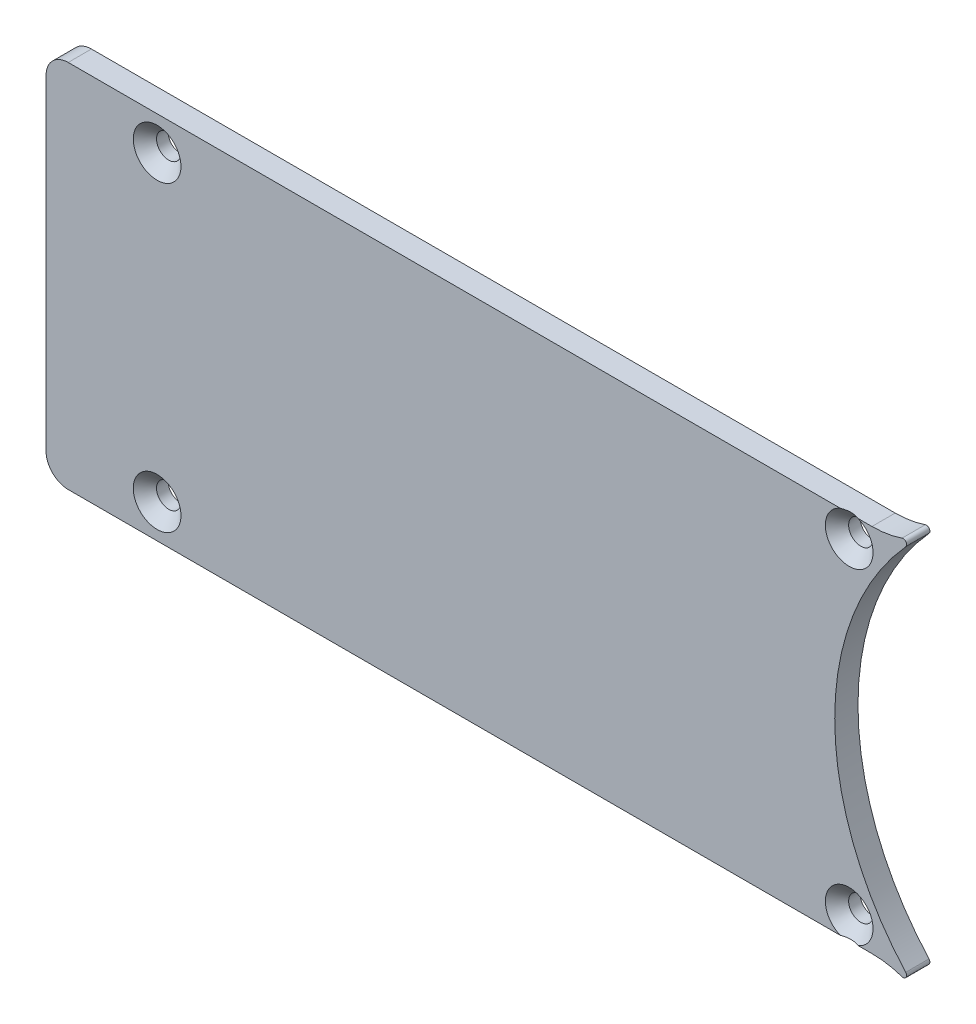
SolidWorks part; units mm, degrees
ref_plane "前视基准面" through (0, 0, 0) normal (0, 0, 1) x (1, 0, 0)
ref_plane "上视基准面" through (0, 0, 0) normal (0, 1, 0) x (1, 0, 0)
ref_plane "右视基准面" through (0, 0, 0) normal (1, 0, 0) x (0, 0, -1)
sketch "草图1" plane through (0, 0, -0.4966) normal (0, 0, 1) x (1, 0, 0)
  line L2 (-91.4, -10.1) -> (-91.4, -14)
  line L3 (-89.5, -15.9) -> (-20.4022, -15.9)
  line L4 (-20.4022, 15.9) -> (-89.5, 15.9)
  line L5 (-91.4, 14) -> (-91.4, 10.1)
  line L8 (-91.4, 10.1) -> (-91.4, -10.1)
  arc A3 (-91.4, -14) -> (-89.5, -15.9) centre (-89.5, -14) ccw
  arc A5 (-17.8134, -16.3248) -> (-20.4022, -15.9) centre (-20.4022, -24) ccw
  arc A16 (-23.6, 0) -> (-17.4951, -15.8392) centre (0, 0) ccw
  arc A17 (-17.4951, 15.8392) -> (-23.6, 0) centre (0, 0) ccw
  arc A18 (-20.4022, 15.9) -> (-17.8134, 16.3248) centre (-20.4022, 24) ccw
  arc A19 (-89.5, 15.9) -> (-91.4, 14) centre (-89.5, 14) ccw
  arc A20 (-17.4951, 15.8392) -> (-17.8134, 16.3248) centre (-17.7175, 16.0406) ccw
  arc A21 (-17.8134, -16.3248) -> (-17.4951, -15.8392) centre (-17.7175, -16.0406) ccw
  circle A24 centre (-81.856, 13) radius 1.05
  circle A25 centre (-81.856, 13) radius 1.05
  circle A39 centre (-81.856, -13) radius 1.05
  circle A40 centre (-81.856, -13) radius 1.05
  circle A42 centre (-22.356, -14) radius 1.05
  circle A43 centre (-22.356, -14) radius 1.05
  circle A45 centre (-22.356, 14) radius 1.05
  circle A46 centre (-22.356, 14) radius 1.05
  dimension "D1" = 0.3
  dimension "D2" = 0.1
  dimension "D3" = 0.1
  dimension "D4" = 0.1
  dimension "D5" = 0.1
extrude "凸台-拉伸1" add sketch "草图1" along normal blind 2
sketch "草图2" plane through (0, 0, -0.4966) normal (0, 0, 1) x (1, 0, 0)
  line L0 (-91.4, 0) -> (-22.0793, 0.4611) construction
  line L1 (-66.7396, 11.2306) -> (-46.7396, 11.2306)
  line L2 (-67.7396, 10.2306) -> (-67.7396, -9.7694)
  line L3 (-66.7396, -10.7694) -> (-46.7396, -10.7694)
  line L4 (-45.7396, 10.2306) -> (-45.7396, -9.7694)
  line L5 (-67.7396, 11.2306) -> (-45.7396, -10.7694) construction
  line L6 (-67.7396, -10.7694) -> (-45.7396, 11.2306) construction
  line L7 (-91.4, 14) -> (-91.4, -14) construction
  line L8 (-68.2396, 12.7306) -> (-45.2396, 12.7306)
  line L9 (-44.2396, 11.7306) -> (-44.2396, -11.2694)
  line L10 (-68.2396, -12.2694) -> (-45.2396, -12.2694)
  line L11 (-69.2396, 11.7306) -> (-69.2396, -11.2694)
  line L12 (-67.7396, 11.2306) -> (-67.7396, -10.7694) construction
  line L13 (-67.7396, -10.7694) -> (-45.7396, -10.7694) construction
  line L14 (-45.7396, 11.2306) -> (-45.7396, -10.7694) construction
  line L15 (-67.7396, 11.2306) -> (-45.7396, 11.2306) construction
  line L16 (-69.2396, 12.7306) -> (-44.2396, 12.7306) construction
  line L17 (-44.2396, 12.7306) -> (-44.2396, -12.2694) construction
  line L18 (-69.2396, -12.2694) -> (-44.2396, -12.2694) construction
  line L19 (-69.2396, 12.7306) -> (-69.2396, -12.2694) construction
  arc A0 (-67.7396, -9.7694) -> (-66.7396, -10.7694) centre (-66.7396, -9.7694) ccw
  arc A1 (-46.7396, -10.7694) -> (-45.7396, -9.7694) centre (-46.7396, -9.7694) ccw
  arc A2 (-46.7396, 11.2306) -> (-45.7396, 10.2306) centre (-46.7396, 10.2306) cw
  arc A3 (-66.7396, 11.2306) -> (-67.7396, 10.2306) centre (-66.7396, 10.2306) ccw
  arc A4 (-45.2396, 12.7306) -> (-44.2396, 11.7306) centre (-45.2396, 11.7306) cw
  arc A5 (-44.2396, -11.2694) -> (-45.2396, -12.2694) centre (-45.2396, -11.2694) cw
  arc A6 (-68.2396, -12.2694) -> (-69.2396, -11.2694) centre (-68.2396, -11.2694) cw
  arc A7 (-68.2396, 12.7306) -> (-69.2396, 11.7306) centre (-68.2396, 11.7306) ccw
  point P0 (-56.7396, 0.2306)
  point P11 (-56.7396, 0.2306)
  dimension "D4" = 1
  dimension "D1" = 22
  dimension "D2" = 22
  dimension "D3" = 1.5
extrude "凸台-拉伸2" add sketch "草图2" against normal blind 1.2
chamfer "倒角1" distance 1 angle 45 4 edges at (-80.806, 13, 1.5034) (-80.806, -13, 1.5034) (-21.306, -14, 1.5034) (-21.306, 14, 1.5034)
